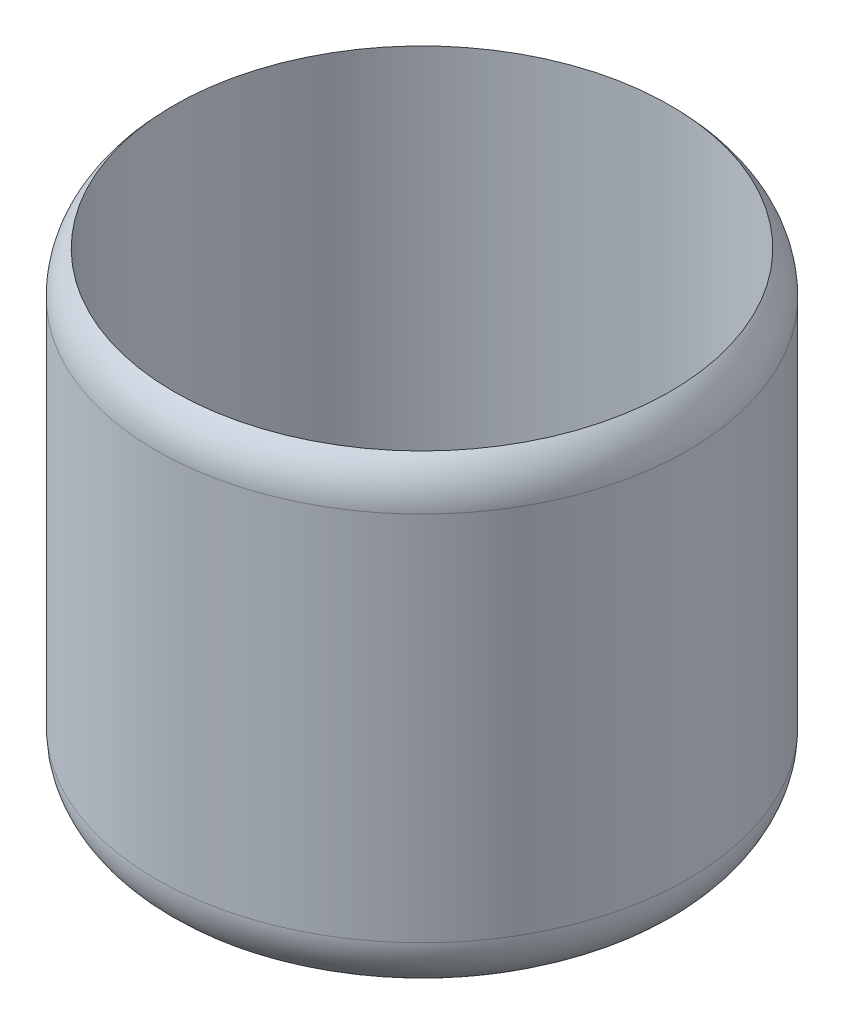
SolidWorks part; units mm, degrees
ref_plane "Front Plane" through (0, 0, 0) normal (0, 0, 1) x (1, 0, 0)
ref_plane "Top Plane" through (0, 0, 0) normal (0, 1, 0) x (1, 0, 0)
ref_plane "Right Plane" through (0, 0, 0) normal (1, 0, 0) x (0, 0, -1)
sketch "Base" plane through (0, 0, 0) normal (0, 1, 0) x (1, 0, 0)
  circle A0 centre (0, 0) radius 22.5
  dimension "D1" = 45
extrude "Boss-Extrude1" add sketch "Base" along normal blind 40
sketch "Sketch2" plane through (0, 40, 0) normal (0, 1, 0) x (1, 0, 0)
  circle A0 centre (0, 0) radius 21
  dimension "D1" = 42
extrude "Cut-Extrude1" cut sketch "Sketch2" against normal blind 37
fillet "Fillet3" radius 5 2 edges at (0, 40, 22.5) (0, 0, 22.5)
